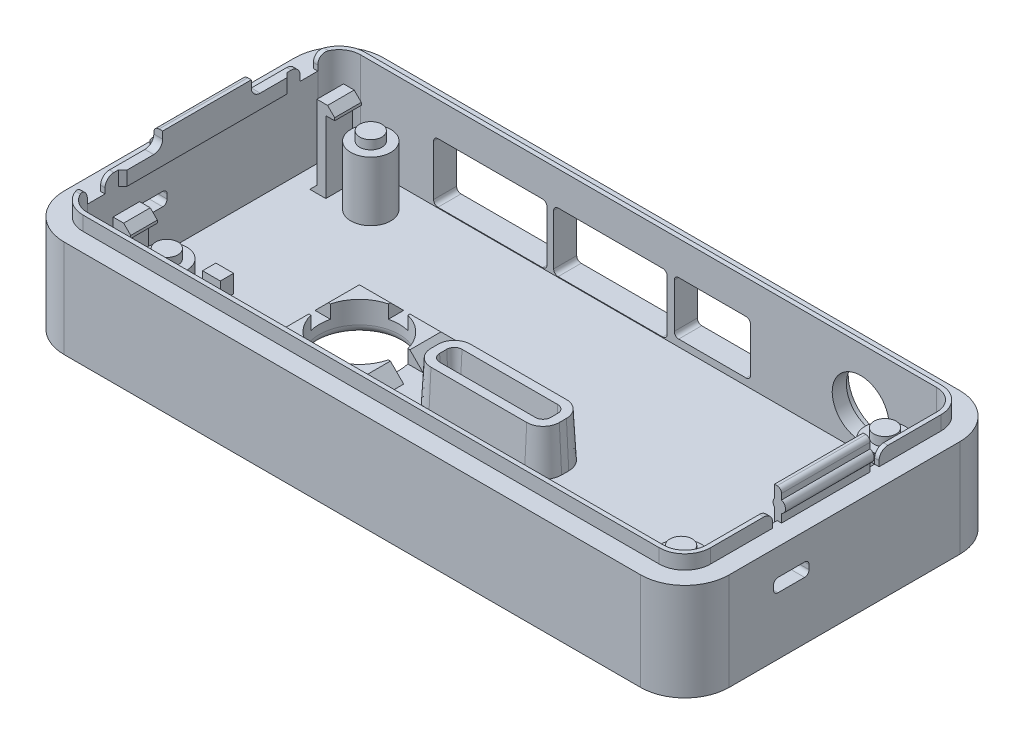
SolidWorks part; units mm, degrees
ref_plane "前视基准面" through (0, 0, 0) normal (0, 0, 1) x (1, 0, 0)
ref_plane "上视基准面" through (0, 0, 0) normal (0, 1, 0) x (1, 0, 0)
ref_plane "右视基准面" through (0, 0, 0) normal (1, 0, 0) x (0, 0, -1)
sketch "zero" plane through (0, 0, 0) normal (0, 1, 0) x (1, 0, 0)
  line L1 (-29.5, 15) -> (29.5, 15)
  line L2 (-32.5, 12) -> (-32.5, -12)
  line L3 (-29.5, -15) -> (29.5, -15)
  line L4 (32.5, 12) -> (32.5, -12)
  line L5 (-32.5, 15) -> (32.5, -15) construction
  line L6 (-32.5, -15) -> (32.5, 15) construction
  line L7 (-25.7, -15) -> (-14.5, -15)
  line L8 (-25.7, -15) -> (-25.7, -9.6569)
  line L9 (-25.7, -9.6569) -> (-14.5, -9.6569)
  line L10 (-14.5, -15) -> (-14.5, -9.6569)
  line L11 (5.2, -15) -> (12.7, -15)
  line L12 (5.2, -15) -> (5.2, -11)
  line L13 (5.2, -11) -> (12.7, -11)
  line L14 (12.7, -15) -> (12.7, -11)
  line L15 (17.8, -15) -> (25.3, -15)
  line L16 (17.8, -15) -> (17.8, -11)
  line L17 (17.8, -11) -> (25.3, -11)
  line L18 (25.3, -15) -> (25.3, -11)
  line L19 (-32.5, 7.7) -> (-19.5, 7.7)
  line L20 (-32.5, 7.7) -> (-32.5, -4.3)
  line L21 (-32.5, -4.3) -> (-19.5, -4.3)
  line L22 (-19.5, 7.7) -> (-19.5, -4.3)
  line L23 (-25.5, 14) -> (25.5, 14)
  line L24 (-25.5, 14) -> (-25.5, 8.8)
  line L25 (-25.5, 8.8) -> (25.5, 8.8)
  line L26 (25.5, 14) -> (25.5, 8.8)
  line L27 (-19.5, 7.2329) -> (-35.5, 7.2329)
  line L28 (-19.5, 7.2329) -> (-19.5, -3.7671)
  line L29 (-19.5, -3.7671) -> (-35.5, -3.7671)
  line L30 (-35.5, 7.2329) -> (-35.5, -3.7671)
  arc A0 (29.5, -15) -> (32.5, -12) centre (29.5, -12) ccw
  arc A1 (29.5, 15) -> (32.5, 12) centre (29.5, 12) cw
  arc A2 (-32.5, -12) -> (-29.5, -15) centre (-29.5, -12) ccw
  arc A3 (-29.5, 15) -> (-32.5, 12) centre (-29.5, 12) ccw
  circle A4 centre (-29, 11.4) radius 3
  circle A5 centre (-29, -11.5) radius 3
  circle A6 centre (29, 11.4) radius 3
  circle A7 centre (29, -11.5) radius 3
  circle A8 centre (-29, 11.4) radius 1.375
  circle A9 centre (-29, -11.5) radius 1.375
  circle A10 centre (29, -11.5) radius 1.375
  circle A11 centre (29, 11.4) radius 1.375
  point P0 (0, 0)
  dimension "D3" = 3
  dimension "D4" = 6
  dimension "D9" = 2.75
  dimension "D1" = 65
  dimension "D2" = 30
  dimension "D5" = 3.6
  dimension "D6" = 3.5
  dimension "D7" = 3.5
  dimension "D8" = 3.5
  dimension "D10" = 12
  dimension "D11" = 7.3
  dimension "D12" = 13
  dimension "D13" = 11.2
  dimension "D14" = 6.8
  dimension "D15" = 19.7
  dimension "D16" = 7.5
  dimension "D17" = 7.5
  dimension "D18" = 5.1
  dimension "D19" = 4
  dimension "D20" = 5.2
  dimension "D21" = 7
  dimension "D22" = 7
  dimension "D23" = 1
  dimension "D24" = 11
  dimension "D25" = 16
sketch "sugar" plane through (0, 0, 0) normal (0, 1, 0) x (1, 0, 0)
  line L1 (-29.5, 15) -> (29.5, 15)
  line L2 (-32.5, 12) -> (-32.5, -12)
  line L3 (-29.5, -15) -> (29.5, -15)
  line L4 (32.5, 12) -> (32.5, -12)
  line L5 (-32.5, 15) -> (32.5, -15) construction
  line L6 (-32.5, -15) -> (32.5, 15) construction
  line L7 (23.5, -11.5) -> (19.5, -11.5)
  line L8 (23.5, -11.5) -> (23.5, -13.9082)
  line L9 (23.5, -13.9082) -> (19.5, -13.9082)
  line L10 (19.5, -11.5) -> (19.5, -13.9082)
  line L11 (16, -11.0071) -> (8.5, -11.0071)
  line L12 (16, -11.0071) -> (16, -15)
  line L13 (16, -15) -> (8.5, -15)
  line L14 (8.5, -11.0071) -> (8.5, -15)
  line L15 (20.5, -13.9082) -> (22.5, -13.9082)
  line L16 (20.5, -13.9082) -> (20.5, -14.8173)
  line L17 (20.5, -14.8173) -> (22.5, -14.8173)
  line L18 (22.5, -13.9082) -> (22.5, -14.8173)
  arc A0 (29.5, 15) -> (32.5, 12) centre (29.5, 12) cw
  arc A1 (29.5, -15) -> (32.5, -12) centre (29.5, -12) ccw
  arc A2 (-32.5, -12) -> (-29.5, -15) centre (-29.5, -12) ccw
  arc A3 (-29.5, 15) -> (-32.5, 12) centre (-29.5, 12) ccw
  circle A4 centre (-29, 11.4) radius 3
  circle A5 centre (-29, 11.4) radius 1.375
  circle A6 centre (-29, -11.5) radius 3
  circle A7 centre (-29, -11.5) radius 1.375
  circle A8 centre (29, 11.4) radius 3
  circle A9 centre (29, 11.4) radius 1.375
  circle A10 centre (29, -11.5) radius 3
  circle A11 centre (29, -11.5) radius 1.375
  dimension "D3" = 3
  dimension "D1" = 65
  dimension "D2" = 30
  dimension "D4" = 9
  dimension "D5" = 4
  dimension "D6" = 3.5
  dimension "D7" = 7.5
  dimension "D8" = 2
  dimension "D9" = 1
sketch "case" plane through (0, 0, 0) normal (0, 1, 0) x (1, 0, 0)
  line L1 (-34.0422, 18) -> (30.9578, 18)
  line L2 (-39.0422, 13) -> (-39.0422, -13)
  line L3 (-34.0422, -18) -> (30.9578, -18)
  line L4 (35.9578, 13) -> (35.9578, -13)
  line L5 (-39.0422, 18) -> (35.9578, -18) construction
  line L6 (-39.0422, -18) -> (35.9578, 18) construction
  arc A0 (-39.0422, -13) -> (-34.0422, -18) centre (-34.0422, -13) ccw
  arc A1 (30.9578, -18) -> (35.9578, -13) centre (30.9578, -13) ccw
  arc A2 (30.9578, 18) -> (35.9578, 13) centre (30.9578, 13) cw
  arc A3 (-34.0422, 18) -> (-39.0422, 13) centre (-34.0422, 13) ccw
  point P0 (-1.5422, 0)
  point P3 (-1.5422, 0)
  dimension "D3" = 5
  dimension "D1" = 75
  dimension "D2" = 36
extrude "凸台-拉伸2" add sketch "case" along normal blind 11
sketch "草图2" plane through (0, 0, 0) normal (0, 1, 0) x (1, 0, 0)
  line L4 (-34.0422, -15.4) -> (30.9578, -15.4)
  line L5 (33.3578, -13) -> (33.3578, 13)
  line L6 (30.9578, 15.4) -> (-34.0422, 15.4)
  line L7 (-36.4422, 13) -> (-36.4422, -13)
  line L8 (33.8578, -13) -> (33.8578, 13)
  line L9 (30.9578, 15.9) -> (-34.0422, 15.9)
  line L10 (-36.9422, 13) -> (-36.9422, -13)
  line L11 (-34.0422, -15.9) -> (30.9578, -15.9)
  line L12 (33.8578, -13) -> (33.8578, 13)
  line L13 (30.9578, 15.9) -> (-34.0422, 15.9)
  line L14 (-36.9422, 13) -> (-36.9422, -13)
  line L15 (-34.0422, -15.9) -> (30.9578, -15.9)
  arc A4 (30.9578, -15.4) -> (33.3578, -13) centre (30.9578, -13) ccw
  arc A5 (33.3578, 13) -> (30.9578, 15.4) centre (30.9578, 13) ccw
  arc A6 (-34.0422, 15.4) -> (-36.4422, 13) centre (-34.0422, 13) ccw
  arc A7 (-36.4422, -13) -> (-34.0422, -15.4) centre (-34.0422, -13) ccw
  arc A8 (30.9578, -15.9) -> (33.8578, -13) centre (30.9578, -13) ccw
  arc A9 (33.8578, 13) -> (30.9578, 15.9) centre (30.9578, 13) ccw
  arc A10 (-34.0422, 15.9) -> (-36.9422, 13) centre (-34.0422, 13) ccw
  arc A11 (-36.9422, -13) -> (-34.0422, -15.9) centre (-34.0422, -13) ccw
  arc A12 (30.9578, -15.9) -> (33.8578, -13) centre (30.9578, -13) ccw
  arc A13 (33.8578, 13) -> (30.9578, 15.9) centre (30.9578, 13) ccw
  arc A14 (-34.0422, 15.9) -> (-36.9422, 13) centre (-34.0422, 13) ccw
  arc A15 (-36.9422, -13) -> (-34.0422, -15.9) centre (-34.0422, -13) ccw
  dimension "D1" = 2.1
  dimension "D2" = 0.5
ref_plane "基准面1" through (0, 11, 0) normal (0, 1, 0) x (1, 0, 0)
sketch "草图3" plane through (0, 11, 0) normal (0, 1, 0) x (1, 0, 0)
  line L4 (-34.0422, -15.4) -> (30.9578, -15.4)
  line L5 (33.3578, -13) -> (33.3578, 13)
  line L6 (30.9578, 15.4) -> (-34.0422, 15.4)
  line L7 (-36.4422, 13) -> (-36.4422, -13)
  line L8 (-34.0422, -15.4) -> (30.9578, -15.4)
  line L9 (33.3578, -13) -> (33.3578, 13)
  line L10 (30.9578, 15.4) -> (-34.0422, 15.4)
  line L11 (-36.4422, 13) -> (-36.4422, -13)
  line L12 (-36.9422, 13) -> (-36.9422, -13)
  line L13 (-34.0422, -15.9) -> (30.9578, -15.9)
  line L14 (33.8578, -13) -> (33.8578, 13)
  line L15 (30.9578, 15.9) -> (-34.0422, 15.9)
  line L16 (-36.9422, 13) -> (-36.9422, -13)
  line L17 (-34.0422, -15.9) -> (30.9578, -15.9)
  line L18 (33.8578, -13) -> (33.8578, 13)
  line L19 (30.9578, 15.9) -> (-34.0422, 15.9)
  arc A4 (30.9578, -15.4) -> (33.3578, -13) centre (30.9578, -13) ccw
  arc A5 (33.3578, 13) -> (30.9578, 15.4) centre (30.9578, 13) ccw
  arc A6 (-34.0422, 15.4) -> (-36.4422, 13) centre (-34.0422, 13) ccw
  arc A7 (-36.4422, -13) -> (-34.0422, -15.4) centre (-34.0422, -13) ccw
  arc A8 (30.9578, -15.4) -> (33.3578, -13) centre (30.9578, -13) ccw
  arc A9 (33.3578, 13) -> (30.9578, 15.4) centre (30.9578, 13) ccw
  arc A10 (-34.0422, 15.4) -> (-36.4422, 13) centre (-34.0422, 13) ccw
  arc A11 (-36.4422, -13) -> (-34.0422, -15.4) centre (-34.0422, -13) ccw
  arc A12 (-36.9422, -13) -> (-34.0422, -15.9) centre (-34.0422, -13) ccw
  arc A13 (30.9578, -15.9) -> (33.8578, -13) centre (30.9578, -13) ccw
  arc A14 (33.8578, 13) -> (30.9578, 15.9) centre (30.9578, 13) ccw
  arc A15 (-34.0422, 15.9) -> (-36.9422, 13) centre (-34.0422, 13) ccw
  arc A16 (-36.9422, -13) -> (-34.0422, -15.9) centre (-34.0422, -13) ccw
  arc A17 (30.9578, -15.9) -> (33.8578, -13) centre (30.9578, -13) ccw
  arc A18 (33.8578, 13) -> (30.9578, 15.9) centre (30.9578, 13) ccw
  arc A19 (-34.0422, 15.9) -> (-36.9422, 13) centre (-34.0422, 13) ccw
  dimension "D1" = 0
  dimension "D2" = 0
extrude "凸台-拉伸4" add sketch "草图3" along normal blind 1.6
sketch "草图5" plane through (0, 11, 0) normal (0, 1, 0) x (1, 0, 0)
  line L0 (33.3578, -13) -> (33.3578, 13) construction
  line L1 (33.0578, 5) -> (33.3578, 5)
  line L2 (33.0578, 5) -> (33.0578, -5)
  line L3 (33.0578, -5) -> (33.3578, -5)
  line L4 (33.3578, 5) -> (33.3578, -5)
  line L5 (33.0578, 5) -> (33.3578, -5) construction
  line L6 (33.0578, -5) -> (33.3578, 5) construction
  point P0 (33.2078, 0)
  dimension "D2" = 10
  dimension "D3" = 0.3
  dimension "D4" = 0
ref_plane "基准面3" through (33.8578, 0, 0) normal (1, 0, 0) x (0, 0, -1)
ref_plane "基准面7" through (-36.9422, 0, 0) normal (-1, 0, 0) x (0, 0, 1)
ref_plane "基准面8" through (0, 0, 0) normal (0, -1, 0) x (-1, 0, 0)
sketch "草图14" plane through (0, 11, 0) normal (0, 1, 0) x (1, 0, 0)
  line L4 (-34.0422, -15.4) -> (30.9578, -15.4)
  line L5 (33.3578, -13) -> (33.3578, 13)
  line L6 (30.9578, 15.4) -> (-34.0422, 15.4)
  line L7 (-36.4422, 13) -> (-36.4422, -13)
  line L8 (-34.0422, -15.4) -> (30.9578, -15.4)
  line L9 (33.3578, -13) -> (33.3578, 13)
  line L10 (30.9578, 15.4) -> (-34.0422, 15.4)
  line L11 (-36.4422, 13) -> (-36.4422, -13)
  arc A4 (30.9578, -15.4) -> (33.3578, -13) centre (30.9578, -13) ccw
  arc A5 (33.3578, 13) -> (30.9578, 15.4) centre (30.9578, 13) ccw
  arc A6 (-34.0422, 15.4) -> (-36.4422, 13) centre (-34.0422, 13) ccw
  arc A7 (-36.4422, -13) -> (-34.0422, -15.4) centre (-34.0422, -13) ccw
  arc A8 (30.9578, -15.4) -> (33.3578, -13) centre (30.9578, -13) ccw
  arc A9 (33.3578, 13) -> (30.9578, 15.4) centre (30.9578, 13) ccw
  arc A10 (-34.0422, 15.4) -> (-36.4422, 13) centre (-34.0422, 13) ccw
  arc A11 (-36.4422, -13) -> (-34.0422, -15.4) centre (-34.0422, -13) ccw
  dimension "D1" = 0
extrude "切除-拉伸2" cut sketch "草图14" against normal blind 9
extrude "凸台-拉伸12" add sketch "草图5" against normal blind 2 and the other way blind 1.6
sketch "草图15" plane through (0, 2, 0) normal (0, 1, 0) x (1, 0, 0)
  line L1 (35.9578, -13) -> (35.9578, 13) construction
  line L5 (-39.0422, 13) -> (-39.0422, -13) construction
  line L6 (-34.0422, -18) -> (30.9578, -18) construction
  line L7 (30.9578, 18) -> (-34.0422, 18) construction
  circle A0 centre (29.0603, -11.5295) radius 2.25
  circle A1 centre (-28.9397, -11.5295) radius 2.25
  circle A2 centre (29.0603, 11.4705) radius 2.25
  circle A3 centre (-28.9397, 11.4705) radius 2.25
  dimension "D1" = 4.5
  dimension "D2" = 6.8975
  dimension "D3" = 10.1025
  dimension "D4" = 6.4705
  dimension "D5" = 6.5295
extrude "凸台-拉伸13" add sketch "草图15" along normal blind 6.7
sketch "草图16" plane through (0, 8.7, 0) normal (0, 1, 0) x (1, 0, 0)
  circle A0 centre (29.0603, -11.5295) radius 1.25
  circle A1 centre (29.0603, 11.4705) radius 1.25
  circle A2 centre (-28.9397, -11.5295) radius 1.25
  circle A3 centre (-28.9397, 11.4705) radius 1.25
  dimension "D1" = 2.5
extrude "凸台-拉伸14" add sketch "草图16" along normal blind 1
sketch "草图17" plane through (0, 12.6, 0) normal (0, 1, 0) x (1, 0, 0)
  line L0 (33.3578, -13) -> (33.3578, -5) construction
  line L1 (33.3578, -5) -> (33.8578, -5)
  line L2 (33.3578, -5) -> (33.3578, -6)
  line L3 (33.3578, -6) -> (33.8578, -6)
  line L4 (33.8578, -5) -> (33.8578, -6)
  line L5 (33.3578, -13) -> (33.3578, 13) construction
  line L6 (33.8578, -13) -> (33.8578, 13) construction
  line L8 (33.3578, 5) -> (33.8578, 5)
  line L9 (33.3578, 5) -> (33.3578, 6)
  line L10 (33.3578, 6) -> (33.8578, 6)
  line L11 (33.8578, 5) -> (33.8578, 6)
  dimension "D1" = 1
  dimension "D2" = 1
extrude "切除-拉伸3" cut sketch "草图17" against normal blind 1.6
sketch "草图19" plane through (0, 12.6, 0) normal (0, 1, 0) x (1, 0, 0)
  line L0 (33.0578, 5) -> (33.0578, -5) construction
  line L1 (33.8578, -5) -> (33.0578, -5)
  line L2 (33.8578, -5) -> (33.8578, 5)
  line L3 (33.8578, 5) -> (33.0578, 5)
  line L4 (33.0578, -5) -> (33.0578, 5)
extrude "凸台-拉伸15" add sketch "草图19" along normal blind 1.8
sketch "草图20" plane through (0, 0, -5) normal (0, 0, -1) x (-1, 0, 0)
  line L0 (-30.9578, 11) -> (-35.9578, 11) construction
  line L3 (-33.8578, 11) -> (-33.8578, 14.4) construction
  circle A0 centre (-33.6078, 12.6) radius 0.7
  dimension "D1" = 1.4
  dimension "D2" = 1.6
  dimension "D3" = 0.25
extrude "凸台-拉伸16" add sketch "草图20" against normal blind 10
fillet "圆角4" radius 0.5 1 edges at (33.8578, 14.4, 0)
sketch "草图39" plane through (0, 0, -18) normal (0, 0, -1) x (-1, 0, 0)
  line L0 (-30.9578, 0) -> (34.0422, 0) construction
  line L1 (-35.9578, 11) -> (-35.9578, 0) construction
  circle A0 centre (-22.3721, 6.2789) radius 4
  dimension "D1" = 6.2789
  dimension "D3" = 8
  dimension "D2" = 13.5857
extrude "切除-拉伸4" cut sketch "草图39" against normal blind 1
sketch "草图41" plane through (0, 0, -18) normal (0, 0, -1) x (-1, 0, 0)
  line L0 (-30.9578, 0) -> (34.0422, 0) construction
  line L1 (-9.9578, 2.7789) -> (-1.3578, 2.7789)
  line L2 (-9.9578, 2.7789) -> (-9.9578, 8.7789)
  line L3 (-9.9578, 8.7789) -> (-1.3578, 8.7789)
  line L4 (-1.3578, 2.7789) -> (-1.3578, 8.7789)
  line L5 (-0.5578, 2.0789) -> (12.2422, 2.0789)
  line L6 (-0.5578, 2.0789) -> (-0.5578, 8.7789)
  line L7 (-0.5578, 8.7789) -> (12.2422, 8.7789)
  line L8 (12.2422, 2.0789) -> (12.2422, 8.7789)
  line L9 (12.9922, 2.0789) -> (25.7922, 2.0789)
  line L10 (12.9922, 2.0789) -> (12.9922, 8.7789)
  line L11 (12.9922, 8.7789) -> (25.7922, 8.7789)
  line L12 (25.7922, 2.0789) -> (25.7922, 8.7789)
  line L13 (-35.9578, 11) -> (-35.9578, 0) construction
  dimension "D1" = 8.7789
  dimension "D2" = 26
  dimension "D3" = 8.6
  dimension "D4" = 6
  dimension "D5" = 0.8
  dimension "D6" = 6.7
  dimension "D7" = 12.8
  dimension "D8" = 0.75
  dimension "D9" = 12.8
extrude "切除-拉伸5" cut sketch "草图41" against normal blind 12
sketch "草图42" plane through (0, 0, -17) normal (0, 0, -1) x (-1, 0, 0)
  circle A0 centre (-22.3721, 6.2789) radius 3.2
  circle A1 centre (-22.3721, 6.2789) radius 4 construction
extrude "切除-拉伸6" cut sketch "草图42" against normal blind 1.6
sketch "草图46" plane through (-36.4422, 0, 0) normal (1, 0, 0) x (0, 0, -1)
  line L0 (13, 12.6) -> (-13, 12.6) construction
  line L1 (-10, 12.6) -> (10, 12.6)
  line L2 (-10, 12.6) -> (-10, 11)
  line L3 (-10, 11) -> (10, 11)
  line L4 (10, 12.6) -> (10, 11)
  line L6 (-18, 11) -> (-18, 0) construction
  dimension "D1" = 8
  dimension "D2" = 8
extrude "凸台-拉伸19" add sketch "草图46" along normal blind 0.5
chamfer "倒角3" distance 1 angle 45 2 edges at (-35.9422, 11.8, -10) (-35.9422, 11.8, 10)
sketch "草图48" plane through (0, 12.6, 0) normal (0, 1, 0) x (1, 0, 0)
  line L0 (-35.9422, 9) -> (-35.9422, -9) construction
  line L1 (-35.9422, -5) -> (-36.9422, -5)
  line L2 (-35.9422, -5) -> (-35.9422, 5)
  line L3 (-35.9422, 5) -> (-36.9422, 5)
  line L4 (-36.9422, -5) -> (-36.9422, 5)
  line L5 (-36.9422, 13) -> (-36.9422, -13) construction
extrude "凸台-拉伸21" add sketch "草图48" along normal blind 1.8
sketch "草图49" plane through (0, 0, 5) normal (0, 0, 1) x (1, 0, 0)
  line L0 (-34.0422, 11) -> (-39.0422, 11) construction
  line L1 (-36.9422, 14.4) -> (-36.9422, 12.6) construction
  circle A0 centre (-36.6922, 12.6) radius 0.7
  dimension "D1" = 1.4
  dimension "D2" = 1.6
  dimension "D3" = 0.25
extrude "凸台-拉伸22" add sketch "草图49" against normal blind 10
sketch "草图50" plane through (0, 12.6, 0) normal (0, 1, 0) x (1, 0, 0)
  line L0 (-36.4422, 13) -> (-36.4422, 9.5) construction
  line L1 (-36.4422, 13) -> (-36.9422, 13)
  line L2 (-36.4422, 13) -> (-36.4422, 11)
  line L3 (-36.4422, 11) -> (-36.9422, 11)
  line L4 (-36.9422, 13) -> (-36.9422, 11)
  line L5 (-36.9422, 13) -> (-36.9422, 5) construction
  line L6 (-36.4422, -9.5) -> (-36.4422, -13) construction
  line L7 (-36.4422, -11) -> (-36.9422, -11)
  line L8 (-36.4422, -11) -> (-36.4422, -13)
  line L9 (-36.4422, -13) -> (-36.9422, -13)
  line L10 (-36.9422, -11) -> (-36.9422, -13)
  line L11 (-36.9422, -5) -> (-36.9422, -13) construction
  line L12 (30.9578, 18) -> (-34.0422, 18) construction
  line L13 (-34.0422, -18) -> (30.9578, -18) construction
  dimension "D1" = 2
  dimension "D2" = 2
  dimension "D3" = 5
  dimension "D4" = 5
extrude "切除-拉伸10" cut sketch "草图50" against normal blind 1.6
fillet "圆角9" radius 1 6 edges at (33.6078, 12.6, 6) (33.6078, 12.6, -6) (-36.6922, 12.6, -13) (-36.6922, 12.6, -11) (-36.6922, 12.6, 11) (-36.6922, 12.6, 13)
fillet "圆角10" radius 0.6 1 edges at (-36.9422, 14.4, 0)
sketch "草图51" plane through (0, 0, 0) normal (0, -1, 0) x (1, 0, 0)
  line L0 (35.9578, 13) -> (35.9578, -13) construction
  line L1 (6.2578, 2.3) -> (-5.7422, 2.3)
  line L2 (6.2578, 2.3) -> (6.2578, 4.3)
  line L3 (6.2578, 4.3) -> (-5.7422, 4.3)
  line L4 (-5.7422, 2.3) -> (-5.7422, 4.3)
  line L5 (30.9578, -18) -> (-34.0422, -18) construction
  dimension "D1" = 2
  dimension "D2" = 12
  dimension "D3" = 29.7
  dimension "D4" = 20.3
extrude "切除-拉伸11" cut sketch "草图51" against normal blind 2
fillet "圆角13" radius 0.6 4 edges at (-5.7422, 1, 4.3) (-5.7422, 1, 2.3) (6.2578, 1, 4.3) (6.2578, 1, 2.3)
sketch "草图52" plane through (0, 2, 0) normal (0, 1, 0) x (1, 0, 0)
  line L0 (-11.5279, -7.2295) -> (-20.7279, -7.2295)
  line L5 (-20.7279, -7.2295) -> (-20.7279, 1.9705)
  line L6 (-11.5279, 1.9705) -> (-20.7279, 1.9705)
  line L7 (-11.5279, -7.2295) -> (-11.5279, 1.9705)
  line L8 (-39.0422, 13) -> (-39.0422, -13) construction
  line L9 (-34.0422, -18) -> (30.9578, -18) construction
  dimension "D1" = 9.2
  dimension "D2" = 9.2
  dimension "D3" = 18.3143
  dimension "D4" = 10.7705
extrude "凸台-拉伸23" add sketch "草图52" along normal blind 1.5
chamfer "倒角5" distance 1.5 angle 45 4 edges at (-16.1279, 2, -1.9705) (-11.5279, 2, 2.6295) (-16.1279, 2, 7.2295) (-20.7279, 2, 2.6295)
sketch "草图53" plane through (0, 0, 0) normal (0, -1, 0) x (1, 0, 0)
  line L1 (30.9578, -18) -> (-34.0422, -18) construction
  line L2 (-39.0422, -13) -> (-39.0422, 13) construction
  circle A0 centre (-16.1279, 2.6295) radius 4.5
  dimension "D1" = 9
  dimension "D2" = 20.6295
  dimension "D3" = 22.9143
extrude "切除-拉伸12" cut sketch "草图53" against normal up to next
fillet "圆角14" radius 1 1 edges at (-16.1279, 0, -1.8705)
sketch "草图55" plane through (0, 3.5, 0) normal (0, 1, 0) x (1, 0, 0)
  line L1 (-10.0279, -3.7295) -> (-22.2279, -3.7295)
  line L2 (-10.0279, -3.7295) -> (-10.0279, -1.5295)
  line L3 (-10.0279, -1.5295) -> (-22.2279, -1.5295)
  line L4 (-22.2279, -3.7295) -> (-22.2279, -1.5295)
  line L5 (-10.0279, -3.7295) -> (-22.2279, -1.5295) construction
  line L6 (-10.0279, -1.5295) -> (-22.2279, -3.7295) construction
  circle A0 centre (-16.1279, -2.6295) radius 4.5 construction
  point P0 (-16.1279, -2.6295)
  dimension "D1" = 12.2
  dimension "D2" = 2.2
extrude "切除-拉伸13" cut sketch "草图55" against normal blind 1.5
sketch "草图56" plane through (0, 3.5, 0) normal (0, 1, 0) x (1, 0, 0)
  line L1 (-15.0279, -8.7295) -> (-17.2279, -8.7295)
  line L2 (-15.0279, -8.7295) -> (-15.0279, 3.4705)
  line L3 (-15.0279, 3.4705) -> (-17.2279, 3.4705)
  line L4 (-17.2279, -8.7295) -> (-17.2279, 3.4705)
  line L5 (-15.0279, -8.7295) -> (-17.2279, 3.4705) construction
  line L6 (-15.0279, 3.4705) -> (-17.2279, -8.7295) construction
  arc A0 (-11.7644, -3.7295) -> (-11.7644, -1.5295) centre (-16.1279, -2.6295) ccw construction
  point P0 (-16.1279, -2.6295)
  dimension "D1" = 12.2
  dimension "D2" = 2.2
extrude "切除-拉伸14" cut sketch "草图56" against normal blind 1.5
sketch "草图62" plane through (0, 0, 0) normal (0, -1, 0) x (1, 0, 0)
  line L54 (31.3299, 13.3324) -> (30.9169, 13.5642)
  line L55 (30.9169, 13.5642) -> (28.7745, 14.7678)
  line L56 (28.7745, 14.7678) -> (28.3615, 15.0024)
  line L57 (27.5011, 14.9926) -> (27.0935, 14.7486)
  line L58 (27.0935, 14.7486) -> (24.9793, 13.4962)
  line L60 (24.9793, 13.4962) -> (24.5717, 13.255)
  line L61 (24.15, 12.5065) -> (24.189, 9.0989)
  line L62 (24.6278, 8.3602) -> (25.0408, 8.1284)
  line L63 (25.0408, 8.1284) -> (27.1831, 6.9248)
  line L65 (27.1831, 6.9248) -> (27.5962, 6.6902)
  line L66 (28.4566, 6.7) -> (28.8641, 6.9441)
  line L67 (28.8641, 6.9441) -> (30.9784, 8.1964)
  line L68 (30.9784, 8.1964) -> (31.3859, 8.4376)
  line L69 (31.8076, 9.1861) -> (31.7686, 12.5937)
  line L70 (25.1226, 12.9222) -> (27.7378, 14.4738)
  line L73 (28.1396, 14.4784) -> (30.7754, 12.9841)
  line L74 (30.7822, 12.6337) -> (28.2554, 11.0831)
  line L75 (29.0741, 8.5137) -> (28.7797, 8.3451)
  line L76 (28.7517, 8.2963) -> (28.7615, 7.4416)
  line L77 (28.7336, 7.3928) -> (28.1845, 7.0731)
  line L78 (28.1013, 7.1205) -> (28.0711, 9.7589)
  line L79 (28.099, 9.8076) -> (29.0331, 10.3512)
  line L80 (31.0237, 8.7127) -> (30.4803, 8.3959)
  line L81 (30.3971, 8.4434) -> (30.3827, 9.6998)
  line L82 (30.4107, 9.7486) -> (30.9541, 10.0626)
  line L83 (31.0373, 10.0151) -> (31.0517, 8.7615)
  line L84 (29.0341, 9.0205) -> (28.7735, 8.8864)
  line L85 (28.7443, 8.9459) -> (28.7366, 9.6183)
  line L86 (28.7646, 9.6671) -> (29.008, 9.8066)
  line L129 (28.7735, 8.8864) -> (28.7797, 8.3451)
  line L130 (28.7443, 8.9459) -> (28.7517, 8.2963)
  spline S0 degree 3 poles (28.3615, 15.0024) (28.2268, 15.075) (28.0782, 15.1132) (27.93, 15.1115) knots 3 3 3 3 4 4 4 4
  spline S1 degree 3 poles (27.93, 15.1115) (27.7818, 15.1098) (27.6341, 15.0682) (27.5011, 14.9926) knots 4 4 4 4 5 5 5 5
  spline S2 degree 3 poles (24.5717, 13.255) (24.3085, 13.0981) (24.1465, 12.8113) (24.15, 12.5065) knots 8 8 8 8 9 9 9 9
  spline S3 degree 3 poles (24.189, 9.0989) (24.1926, 8.7912) (24.3611, 8.511) (24.6278, 8.3602) knots 10 10 10 10 11 11 11 11
  spline S4 degree 3 poles (27.5962, 6.6902) (27.7309, 6.6148) (27.8795, 6.5794) (28.0277, 6.5811) knots 14 14 14 14 15 15 15 15
  spline S5 degree 3 poles (28.0277, 6.5811) (28.1759, 6.5828) (28.3236, 6.6216) (28.4566, 6.7) knots 15 15 15 15 16 16 16 16
  spline S6 degree 3 poles (31.3859, 8.4376) (31.652, 8.5945) (31.8112, 8.8784) (31.8076, 9.1861) knots 19 19 19 19 20 20 20 20
  spline S7 degree 3 poles (31.7686, 12.5937) (31.7651, 12.8986) (31.5995, 13.1816) (31.3299, 13.3324) knots 21 21 21 21 22 22 22 22
  spline S8 degree 2 poles (27.6998, 11.0768) (25.1072, 12.5345) (25.1014, 12.5373) knots 0 0 0 1 1 1
  spline S9 degree 3 poles (25.1014, 12.5373) (24.9664, 12.6326) (24.9783, 12.838) (25.1226, 12.9222) knots 1 1 1 1 2 2 2 2
  spline S10 degree 3 poles (27.7378, 14.4738) (27.8595, 14.5465) (28.0134, 14.5482) (28.1396, 14.4784) knots 3 3 3 3 4 4 4 4
  spline S11 degree 3 poles (30.7754, 12.9841) (30.9101, 12.9087) (30.9152, 12.715) (30.7822, 12.6337) knots 5 5 5 5 6 6 6 6
  spline S12 degree 3 poles (28.2554, 11.0831) (28.0856, 10.9815) (27.8719, 10.979) (27.6998, 11.0768) knots 7 7 7 7 8 8 8 8
  spline S13 degree 3 poles (28.7615, 7.4416) (28.7618, 7.4216) (28.7534, 7.4044) (28.7336, 7.3928) knots 3 3 3 3 4 4 4 4
  spline S14 degree 3 poles (28.1845, 7.0731) (28.1477, 7.0527) (28.1018, 7.0778) (28.1013, 7.1205) knots 5 5 5 5 6 6 6 6
  spline S15 degree 3 poles (28.0711, 9.7589) (28.0708, 9.7788) (28.0792, 9.7988) (28.099, 9.8076) knots 7 7 7 7 8 8 8 8
  spline S16 degree 3 poles (29.0331, 10.3512) (29.6389, 10.7029) (30.1424, 10.7771) (30.1502, 10.0933) knots 9 9 9 9 10 10 10 10
  spline S17 degree 3 poles (30.1502, 10.0933) (30.1577, 9.4351) (29.6544, 8.8509) (29.0741, 8.5137) knots 10 10 10 10 11 11 11 11
  spline S18 degree 3 poles (31.0517, 8.7615) (31.0519, 8.7415) (31.0407, 8.7214) (31.0237, 8.7127) knots 0 0 0 0 1 1 1 1
  spline S19 degree 3 poles (30.4803, 8.3959) (30.4435, 8.3755) (30.3976, 8.4006) (30.3971, 8.4434) knots 2 2 2 2 3 3 3 3
  spline S20 degree 3 poles (30.3827, 9.6998) (30.3825, 9.7198) (30.3937, 9.737) (30.4107, 9.7486) knots 4 4 4 4 5 5 5 5
  spline S21 degree 3 poles (30.9541, 10.0626) (30.991, 10.0829) (31.0368, 10.0578) (31.0373, 10.0151) knots 6 6 6 6 7 7 7 7
  spline S22 degree 3 poles (30.6996, 10.8946) (30.9175, 11.0224) (31.0748, 10.9701) (31.0771, 10.7707) (31.0794, 10.5741) (30.9253, 10.3415) (30.7073, 10.2165) knots 2 2 2 2 3 3 3 4 4 4 4
  spline S23 degree 3 poles (30.7073, 10.2165) (30.4866, 10.0857) (30.3293, 10.1381) (30.327, 10.3346) (30.3247, 10.5369) (30.4788, 10.7667) (30.6996, 10.8946) knots 0 0 0 0 1 1 1 2 2 2 2
  spline S24 degree 3 poles (29.5048, 9.7183) (29.5079, 9.4476) (29.3569, 9.2065) (29.0341, 9.0205) knots 0 0 0 0 1 1 1 1
  spline S25 degree 3 poles (28.7366, 9.6183) (28.7364, 9.6382) (28.7475, 9.6583) (28.7646, 9.6671) knots 4 4 4 4 5 5 5 5
  spline S26 degree 3 poles (29.008, 9.8066) (29.325, 9.9926) (29.5016, 9.9975) (29.5048, 9.7183) knots 6 6 6 6 7 7 7 7
fillet "圆角17" radius 1 2 edges at (-36.4422, 12.6, 5) (-36.4422, 12.6, -5)
sketch "草图63" plane through (0, 2, 0) normal (0, 1, 0) x (1, 0, 0)
  line L0 (30.9578, 15.4) -> (-34.0422, 15.4) construction
  line L1 (-30.4422, -4.5) -> (-28.4422, -4.5)
  line L2 (-30.4422, -4.5) -> (-30.4422, -6)
  line L3 (-30.4422, -6) -> (-28.4422, -6)
  line L4 (-28.4422, -4.5) -> (-28.4422, -6)
  line L5 (-36.4422, 13) -> (-36.4422, -13) construction
  dimension "D1" = 2
  dimension "D2" = 1.5
  dimension "D3" = 19.9
  dimension "D4" = 6
extrude "凸台-拉伸24" add sketch "草图63" along normal blind 2
fillet "圆角18" radius 0.5 12 edges at (1.3578, 8.7789, -16.7) (9.9578, 8.7789, -16.7) (9.9578, 2.7789, -16.7) (1.3578, 2.7789, -16.7) (-12.2422, 2.0789, -16.7) (0.5578, 2.0789, -16.7) (0.5578, 8.7789, -16.7) (-12.2422, 8.7789, -16.7) (-25.7922, 8.7789, -16.7) (-12.9922, 8.7789, -16.7) (-25.7922, 2.0789, -16.7) (-12.9922, 2.0789, -16.7)
sketch "草图66" plane through (0, 2, 0) normal (0, 1, 0) x (1, 0, 0)
  line L8 (-5.1422, -0.8) -> (5.6578, -0.8)
  line L9 (-7.2422, -3.7) -> (-7.2422, -2.9)
  line L10 (5.6578, -5.8) -> (-5.1422, -5.8)
  line L11 (7.7578, -2.9) -> (7.7578, -3.7)
  arc A8 (7.7578, -2.9) -> (5.6578, -0.8) centre (5.6578, -2.9) ccw
  arc A9 (-5.1422, -0.8) -> (-7.2422, -2.9) centre (-5.1422, -2.9) ccw
  arc A10 (-7.2422, -3.7) -> (-5.1422, -5.8) centre (-5.1422, -3.7) ccw
  arc A11 (5.6578, -5.8) -> (7.7578, -3.7) centre (5.6578, -3.7) ccw
extrude "凸台-拉伸27" add sketch "草图66" along normal blind 5 draft 3
extrude "切除-拉伸15" cut sketch "草图62" against normal blind 0.5
sketch "草图67" plane through (-39.0422, 0, 0) normal (-1, 0, 0) x (0, 0, 1)
  line L0 (18, 11) -> (18, 0) construction
  line L1 (4, 8) -> (8, 8)
  line L2 (4, 8) -> (4, 6.5)
  line L3 (4, 6.5) -> (8, 6.5)
  line L4 (8, 8) -> (8, 6.5)
  line L5 (-13, 11) -> (13, 11) construction
  dimension "D1" = 4
  dimension "D2" = 1.5
  dimension "D3" = 10
  dimension "D4" = 3
extrude "切除-拉伸16" cut sketch "草图67" against normal up to next
fillet "圆角20" radius 0.5 4 edges at (-37.7422, 6.5, 8) (-37.7422, 8, 8) (-37.7422, 8, 4) (-37.7422, 6.5, 4)
sketch "草图68" plane through (33.3578, 0, 0) normal (-1, 0, 0) x (0, 0, 1)
  line L0 (8, 7) -> (8, 7.5) construction
  line L1 (4.5, 6.5) -> (7.5, 6.5) construction
  line L2 (4, 7.5) -> (4, 7) construction
  line L3 (7.5, 8) -> (4.5, 8) construction
  line L4 (8, 7) -> (8, 7.5)
  line L5 (4.5, 6.5) -> (7.5, 6.5)
  line L6 (4, 7.5) -> (4, 7)
  line L7 (7.5, 8) -> (4.5, 8)
  arc A0 (8, 7.5) -> (7.5, 8) centre (7.5, 7.5) ccw construction
  arc A1 (7.5, 6.5) -> (8, 7) centre (7.5, 7) ccw construction
  arc A2 (4, 7) -> (4.5, 6.5) centre (4.5, 7) ccw construction
  arc A3 (4.5, 8) -> (4, 7.5) centre (4.5, 7.5) ccw construction
  arc A4 (8, 7.5) -> (7.5, 8) centre (7.5, 7.5) ccw
  arc A5 (7.5, 6.5) -> (8, 7) centre (7.5, 7) ccw
  arc A6 (4, 7) -> (4.5, 6.5) centre (4.5, 7) ccw
  arc A7 (4.5, 8) -> (4, 7.5) centre (4.5, 7.5) ccw
extrude "切除-拉伸17" cut sketch "草图68" against normal up to next
sketch "草图70" plane through (0, 2, 0) normal (0, -1, 0) x (1, 0, 0)
  line L0 (5.6578, 4.3) -> (-5.1422, 4.3) construction
  line L1 (-5.7422, 3.7) -> (-5.7422, 2.9) construction
  line L2 (-5.1422, 2.3) -> (5.6578, 2.3) construction
  line L3 (6.2578, 2.9) -> (6.2578, 3.7) construction
  line L4 (6.2578, 2.9) -> (6.2578, 3.7)
  line L5 (-5.1422, 2.3) -> (5.6578, 2.3)
  line L6 (-5.7422, 3.7) -> (-5.7422, 2.9)
  line L7 (5.6578, 4.3) -> (-5.1422, 4.3)
  arc A0 (6.2578, 3.7) -> (5.6578, 4.3) centre (5.6578, 3.7) ccw construction
  arc A1 (-5.1422, 4.3) -> (-5.7422, 3.7) centre (-5.1422, 3.7) ccw construction
  arc A2 (-5.7422, 2.9) -> (-5.1422, 2.3) centre (-5.1422, 2.9) ccw construction
  arc A3 (5.6578, 2.3) -> (6.2578, 2.9) centre (5.6578, 2.9) ccw construction
  arc A4 (6.2578, 3.7) -> (5.6578, 4.3) centre (5.6578, 3.7) ccw
  arc A5 (5.6578, 2.3) -> (6.2578, 2.9) centre (5.6578, 2.9) ccw
  arc A6 (-5.7422, 2.9) -> (-5.1422, 2.3) centre (-5.1422, 2.9) ccw
  arc A7 (-5.1422, 4.3) -> (-5.7422, 3.7) centre (-5.1422, 3.7) ccw
extrude "切除-拉伸18" cut sketch "草图70" against normal up to next (5 mm away) draft 3 draft outward yes
sketch "草图71" plane through (33.3578, 0, 0) normal (-1, 0, 0) x (0, 0, 1)
  line L0 (13, 2) -> (-13, 2) construction
  line L1 (-9, 11) -> (-7, 11)
  line L2 (-9, 11) -> (-9, 10)
  line L3 (-9, 10) -> (-7, 10)
  line L4 (-7, 11) -> (-7, 10)
  line L5 (7, 11) -> (9, 11)
  line L6 (7, 11) -> (7, 10)
  line L7 (7, 10) -> (9, 10)
  line L8 (9, 11) -> (9, 10)
  line L10 (-18, 11) -> (-18, 0) construction
  line L11 (18, 11) -> (18, 0) construction
  dimension "D1" = 2
  dimension "D2" = 2
  dimension "D3" = 1
  dimension "D4" = 8
  dimension "D5" = 9
  dimension "D6" = 9
extrude "凸台-拉伸28" add sketch "草图71" along normal blind 1.8
chamfer "倒角6" distance 0.8 angle 45 2 edges at (31.5578, 11, 8) (31.5578, 11, -8)
sketch "草图73" plane through (0, 2, 0) normal (0, 1, 0) x (1, 0, 0)
  line L0 (30.9578, 18) -> (-34.0422, 18) construction
  line L1 (-33.5422, 13) -> (-32.5422, 13)
  line L2 (-33.5422, 13) -> (-33.5422, 10)
  line L3 (-33.5422, 10) -> (-32.5422, 10)
  line L4 (-32.5422, 13) -> (-32.5422, 10)
  line L5 (-33.5422, -10) -> (-32.5422, -10)
  line L6 (-33.5422, -10) -> (-33.5422, -13)
  line L7 (-33.5422, -13) -> (-32.5422, -13)
  line L8 (-32.5422, -10) -> (-32.5422, -13)
  line L9 (-34.0422, -18) -> (30.9578, -18) construction
  line L10 (-39.0422, 13) -> (-39.0422, -13) construction
  dimension "D1" = 5
  dimension "D2" = 3
  dimension "D3" = 3
  dimension "D4" = 5
  dimension "D5" = 1
  dimension "D6" = 1
  dimension "D7" = 5.5
  dimension "D8" = 5.5
extrude "凸台-拉伸30" add sketch "草图73" along normal blind 9.2
sketch "草图74" plane through (-32.5422, 0, 0) normal (1, 0, 0) x (0, 0, -1)
  line L0 (10, 11.2) -> (10, 2) construction
  line L1 (10, 11.2) -> (13, 11.2)
  line L2 (10, 11.2) -> (10, 10.1)
  line L3 (10, 10.1) -> (13, 10.1)
  line L4 (13, 11.2) -> (13, 10.1)
  line L5 (10, 11.2) -> (13, 11.2) construction
  line L6 (13, 11.2) -> (13, 2) construction
  line L7 (-13, 11.2) -> (-10, 11.2) construction
  line L8 (-13, 11.2) -> (-10, 11.2)
  line L9 (-13, 11.2) -> (-13, 10.1)
  line L10 (-13, 10.1) -> (-10, 10.1)
  line L11 (-10, 11.2) -> (-10, 10.1)
  line L12 (-10, 11.2) -> (-10, 2) construction
  dimension "D1" = 1.1
  dimension "D2" = 1.1
extrude "凸台-拉伸31" add sketch "草图74" along normal blind 1
chamfer "倒角7" distance 0.8 angle 45 4 edges at (-33.5422, 2, 11.5) (-33.5422, 2, -11.5) (-31.5422, 11.2, 11.5) (-31.5422, 11.2, -11.5)
